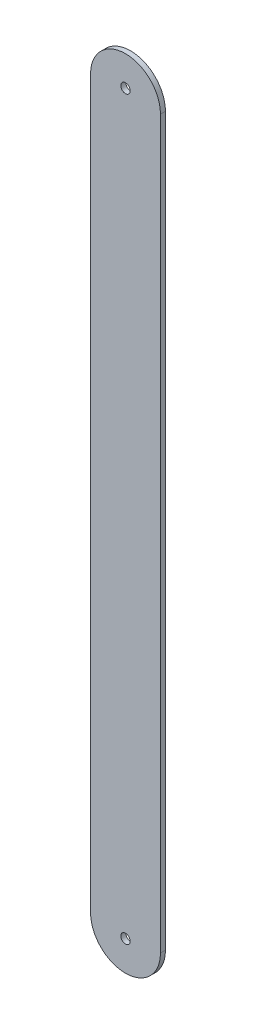
SolidWorks part; units mm, degrees
material "Thornel Mat VMA"
ref_plane "Front Plane" through (0, 0, 0) normal (0, 0, 1) x (1, 0, 0)
ref_plane "Top Plane" through (0, 0, 0) normal (0, 1, 0) x (1, 0, 0)
ref_plane "Right Plane" through (0, 0, 0) normal (1, 0, 0) x (0, 0, -1)
sketch "Sketch1" plane through (0, 0, 0) normal (0, 0, 1) x (1, 0, 0)
  line L0 (0, 115.5186) -> (0, -115.5186) construction
  line L1 (-11.1125, 115.5186) -> (11.1125, 115.5186)
  line L2 (-11.1125, 115.5186) -> (-11.1125, -115.5186)
  line L3 (-11.1125, -115.5186) -> (11.1125, -115.5186)
  line L4 (11.1125, 115.5186) -> (11.1125, -115.5186)
  arc A0 (-11.1125, 115.5186) -> (11.1125, 115.5186) centre (0, 115.5186) cw
  arc A1 (-11.1125, -115.5186) -> (11.1125, -115.5186) centre (0, -115.5186) ccw
  circle A2 centre (0, -117.1061) radius 1.5
  circle A3 centre (0, 117.1061) radius 1.5
  point P10 (0, 126.6311)
  point P11 (0, -126.6311)
  point P14 (0, 0)
  dimension "D2" = 253.2621
  dimension "D5" = 3
  dimension "D6" = 3
  dimension "D1" = 22.225
  dimension "D3" = 9.525
  dimension "D4" = 9.525
extrude "Boss-Extrude1" add sketch "Sketch1" along normal blind 1.5875 contours A0 L1 A3 | L1 L0 L3 L4 | L0 L1 L2 L3 | L3 A1 A2 region at (5.5562, 0, 0) region at (-5.5563, 0, 0) region at (0, 120.3532, 0) region at (0, -120.3532, 0)
